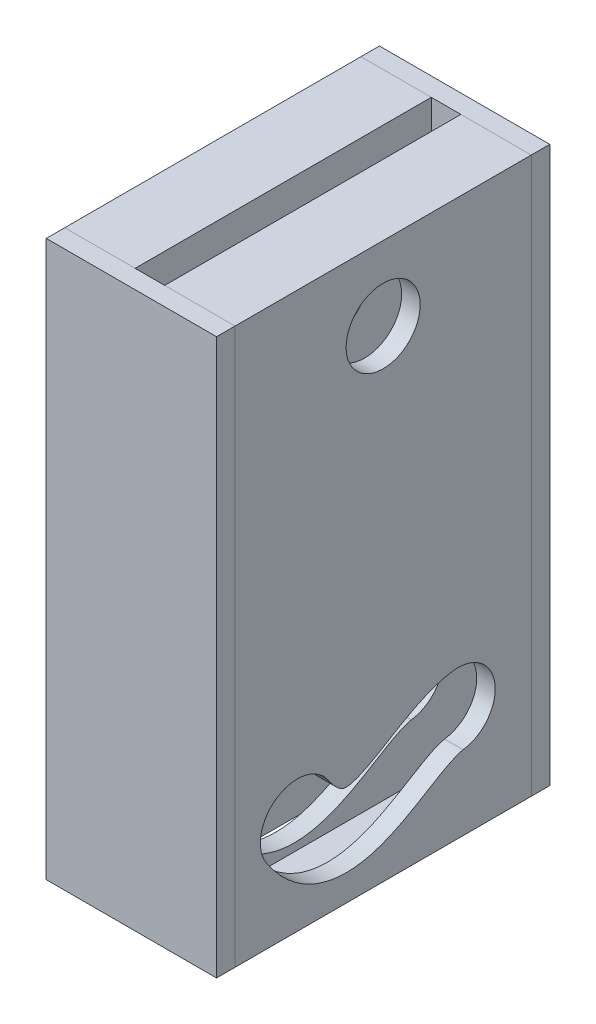
SolidWorks part; units mm, degrees
ref_plane "Front Plane" through (0, 0, 0) normal (0, 0, 1) x (1, 0, 0)
ref_plane "Top Plane" through (0, 0, 0) normal (0, 1, 0) x (1, 0, 0)
ref_plane "Right Plane" through (0, 0, 0) normal (1, 0, 0) x (0, 0, -1)
sketch "Sketch1" plane through (0, 0, 0) normal (0, 0, 1) x (1, 0, 0)
  line L0 (-4, 75) -> (-4, 35)
  line L8 (-4, -35) -> (-4, -75)
  line L9 (-4, -75) -> (-23, -75)
  line L10 (-23, -75) -> (-23, 75)
  line L11 (-23, 75) -> (-4, 75)
  line L12 (0, 171.0434) -> (0, -171.0434) construction
  line L13 (-4, 35) -> (4, 35)
  line L14 (-4, -35) -> (4, -35)
  line L15 (4, -35) -> (4, -75)
  line L16 (4, -75) -> (23, -75)
  line L17 (23, -75) -> (23, 75)
  line L18 (4, 75) -> (4, 35)
  line L19 (23, 75) -> (4, 75)
  line L20 (-18, 70) -> (-9, 70)
  line L21 (-9, 70) -> (-9, 30)
  line L22 (-9, 30) -> (9, 30)
  line L23 (9, 70) -> (9, 30)
  line L24 (18, 70) -> (9, 70)
  line L25 (18, -70) -> (18, 70)
  line L26 (9, -70) -> (18, -70)
  line L27 (9, -30) -> (9, -70)
  line L28 (-9, -30) -> (9, -30)
  line L29 (-9, -30) -> (-9, -70)
  line L30 (-9, -70) -> (-18, -70)
  line L31 (-18, -70) -> (-18, 70)
  line L32 (-71.2515, 55) -> (71.2515, 55) construction
  line L33 (-18, 0) -> (18, 0) construction
  line L34 (-23, 65) -> (23, 65) construction
  line L35 (-23, -65) -> (23, -65) construction
  line L36 (-71.2515, -55) -> (71.2515, -55) construction
  point P6 (0, -35)
  point P16 (0, 35)
  point P31 (0, 0)
  point P34 (0, 55)
  point P35 (-4, 55)
  dimension "D2" = 10
  dimension "D3" = 8
  dimension "D4" = 46
  dimension "D5" = 150
  dimension "D6" = 20
  dimension "D1" = 5
sketch "Sketch2" plane through (0, 0, 0) normal (1, 0, 0) x (0, 0, -1)
  line L0 (-40, 0) -> (40, 0) construction
  line L1 (-40, 0) -> (-45, 0) construction
  line L2 (40, 0) -> (45, 0) construction
  point P4 (0, 0)
  dimension "D1" = 80
  dimension "D2" = 5
extrude "Boss-Extrude1" add sketch "Sketch1" along normal up to vertex (40 mm away) and the other way up to vertex (40 mm away) up to point (0, 0, 40) other way up to point (0, 0, -40)
sketch "Sketch3" plane through (0, 0, 0) normal (0, 0, 1) x (1, 0, 0)
  line L1 (-23, -75) -> (23, -75)
  line L2 (-23, -75) -> (-23, 75)
  line L3 (-23, 75) -> (23, 75)
  line L4 (23, -75) -> (23, 75)
  line L5 (-23, -75) -> (23, 75) construction
  line L6 (-23, 75) -> (23, -75) construction
  point P0 (0, 0)
extrude "Boss-Extrude2" add sketch "Sketch3" along normal up to vertex (45 mm away) from vertex separate body up to point (0, 0, 45) starting at point (0, 0, 40)
extrude "Boss-Extrude3" add sketch "Sketch3<2>" against normal up to vertex (45 mm away) from vertex separate body up to point (0, 0, -45) starting at point (0, 0, -40)
sketch "Sketch3<2>" plane through (0, 0, 0) normal (0, 0, 1) x (1, 0, 0) same geometry as "Sketch3"
sketch "Sketch4" plane through (0, 0, 0) normal (1, 0, 0) x (0, 0, -1)
  line L0 (0, 171.0434) -> (0, -171.0434) construction
  circle A0 centre (0, 55) radius 10
  circle A1 centre (0, -55) radius 10 construction
  arc A2 (-31.4617, -54.9352) -> (-14.8827, -43.7487) centre (-23.1722, -49.342) cw
  arc A3 (21.5877, -54.9129) -> (18.9531, -35.0871) centre (20.2704, -45) ccw
  spline S0 degree 3 poles (-23.1722, -49.342) (-9.1837, -70.0737) (6.7542, -46.7961) (20.2704, -45) knots 0 0 0 0 1 1 1 1 construction
  spline S1 degree 1 poles (-31.4617, -54.9352) (21.5877, -54.9129) knots 0 0 1 1 construction
  spline S2 degree 3 poles (-31.4617, -54.9352) (-30.913, -55.7484) (-29.7473, -57.359) (-27.3068, -60.2469) (-23.9206, -63.3578) (-19.2822, -66.1168) (-14.2588, -67.686) (-9.2968, -68.0371) (-4.7395, -67.4454) (-0.6629, -66.254) (4.2173, -64.2022) (8.4538, -61.802) (12.2348, -59.5117) (14.8357, -57.9446) (17.1724, -56.627) (18.8426, -55.8121) (19.9554, -55.359) (20.6614, -55.1187) (21.1238, -54.997) (21.4202, -54.9377) (21.5283, -54.9208) (21.5877, -54.9129) knots 0 0 0 0 0.03125 0.0625 0.125 0.1875 0.25 0.3125 0.375 0.4375 0.5 0.625 0.6875 0.75 0.8125 0.875 0.90625 0.9375 0.96875 0.984375 1 1 1 1
  spline S3 degree 1 poles (-14.8827, -43.7487) (18.9531, -35.0871) knots 0 0 1 1 construction
  spline S4 degree 3 poles (-14.8827, -43.7487) (-14.732, -43.9721) (-14.4132, -44.428) (-13.827, -45.2053) (-13.1419, -46.0112) (-12.4318, -46.7144) (-11.6443, -47.3576) (-10.9805, -47.7182) (-10.5151, -47.8548) (-9.948, -47.9126) (-8.6179, -47.7812) (-5.7019, -46.7954) (-0.9385, -44.1508) (3.653, -41.2952) (7.7222, -38.9894) (11.0302, -37.353) (14.0932, -36.1732) (16.7705, -35.4494) (18.2306, -35.1832) (18.9531, -35.0871) knots 0 0 0 0 0.015625 0.03125 0.0625 0.09375 0.125 0.1875 0.25 0.3125 0.375 0.5 0.625 0.75 0.8125 0.875 0.9375 0.96875 1 1 1 1
  point P10 (0, -55)
  dimension "D1" = 20
  dimension "D2" = 10
  dimension "D3" = 10
extrude "Cut-Extrude1" cut sketch "Sketch4" against normal through all and the other way through all
